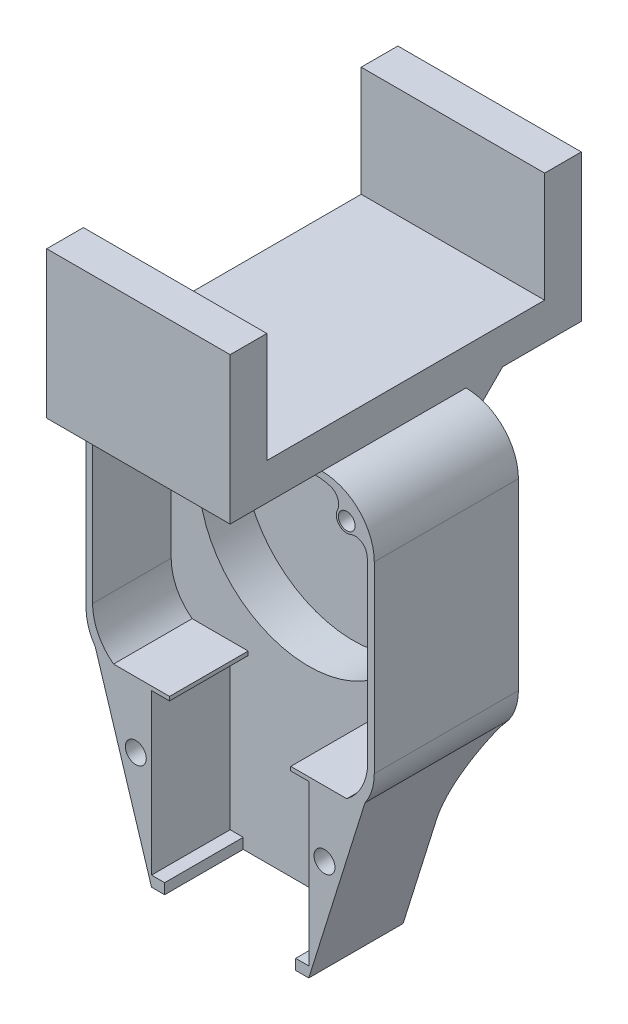
SolidWorks part; units mm, degrees
ref_plane "Alzado" through (0, 0, 0) normal (0, 0, 1) x (1, 0, 0)
ref_plane "Planta" through (0, 0, 0) normal (0, 1, 0) x (1, 0, 0)
ref_plane "Vista lateral" through (0, 0, 0) normal (1, 0, 0) x (0, 0, -1)
sketch "Croquis4" plane through (0, 0, 0) normal (0, 0, 1) x (1, 0, 0)
  line L9 (-17.5, 27.5) -> (17.5, 27.5)
  line L10 (-27.5, 17.5) -> (-27.5, -17.5)
  line L11 (-17.5, -27.5) -> (17.5, -27.5)
  line L12 (27.5, 17.5) -> (27.5, -17.5)
  line L13 (-27.5, 27.5) -> (27.5, -27.5) construction
  line L14 (-27.5, -27.5) -> (27.5, 27.5) construction
  circle A0 centre (0, 0) radius 2.5
  arc A1 (-27.5, -17.5) -> (-17.5, -27.5) centre (-17.5, -17.5) ccw
  arc A2 (17.5, -27.5) -> (27.5, -17.5) centre (17.5, -17.5) ccw
  arc A3 (17.5, 27.5) -> (27.5, 17.5) centre (17.5, 17.5) cw
  arc A4 (-17.5, 27.5) -> (-27.5, 17.5) centre (-17.5, 17.5) ccw
  point P0 (0, 0)
  dimension "D3" = 5
  dimension "D4" = 10
  dimension "D1" = 55
  dimension "D2" = 55
extrude "Saliente-Extruir1" add sketch "Croquis4" along normal blind 4
sketch "Croquis5" plane through (0, 0, 4) normal (0, 0, 1) x (1, 0, 0)
  line L1 (-17.5, 27.5) -> (17.5, 27.5)
  line L2 (-27.5, 17.5) -> (-27.5, -17.5)
  line L3 (-17.5, -27.5) -> (17.5, -27.5)
  line L4 (27.5, 17.5) -> (27.5, -17.5)
  line L5 (-27.5, 27.5) -> (27.5, -27.5) construction
  line L6 (-27.5, -27.5) -> (27.5, 27.5) construction
  circle A0 centre (0, 0) radius 21
  circle A1 centre (0, 0) radius 2.5 construction
  arc A2 (17.5, -27.5) -> (27.5, -17.5) centre (17.5, -17.5) ccw
  arc A3 (-27.5, -17.5) -> (-17.5, -27.5) centre (-17.5, -17.5) ccw
  arc A4 (17.5, 27.5) -> (27.5, 17.5) centre (17.5, 17.5) cw
  arc A5 (-17.5, 27.5) -> (-27.5, 17.5) centre (-17.5, 17.5) ccw
  point P4 (0, 0)
  dimension "D1" = 42
  dimension "D4" = 10
  dimension "D2" = 55
  dimension "D3" = 55
extrude "Saliente-Extruir2" add sketch "Croquis5" along normal blind 8.5
sketch "Croquis6" plane through (0, 0, 12.5) normal (0, 0, 1) x (1, 0, 0)
  line L1 (-25.7206, -23.194) -> (-15, -57.5)
  line L2 (-15, -57.5) -> (15, -57.5)
  line L3 (-17.5, -27.5) -> (17.5, -27.5) construction
  line L4 (15, -57.5) -> (25.7206, -23.194)
  line L8 (-17.5, -27.5) -> (17.5, -27.5)
  line L12 (25.119, -25.119) -> (27.5, -27.5) construction
  arc A1 (17.5, -27.5) -> (25.7206, -23.194) centre (17.5, -17.5) ccw
  arc A2 (-25.7206, -23.194) -> (-17.5, -27.5) centre (-17.5, -17.5) ccw
  point P5 (0, 0)
  dimension "D6" = 10
  dimension "D2" = 30
  dimension "D3" = 30
extrude "Saliente-Extruir4" add sketch "Croquis6" against normal blind 3
fillet "Redondeo1" radius 10 3 edges at (22.1401, -26.3583, 9.5) (-22.1401, -26.3583, 9.5) (0, -27.5, 9.5)
sketch "Croquis8" plane through (0, 0, 12.5) normal (0, 0, 1) x (1, 0, 0)
  line L0 (0, -57.5) -> (0, -20) construction
  line L1 (-15, -57.5) -> (15, -57.5) construction
  line L2 (-25.3906, -24.25) -> (-25.8417, -23.0151)
  line L3 (-15, -55.5) -> (-15, -25)
  line L4 (-17.5, 27.5) -> (17.5, 27.5)
  line L5 (12.5, -55.5) -> (15, -55.5)
  line L6 (-27.5, 17.5) -> (-27.5, -17.5)
  line L7 (-15, -25) -> (-11.5606, -25)
  line L8 (-11.5606, -25) -> (-11.5606, -24.25)
  line L9 (-11.5606, -24.25) -> (-25.3906, -24.25)
  line L10 (12.5, -57.5) -> (12.5, -55.5)
  line L11 (-25.7206, -23.194) -> (-15, -57.5) construction
  line L12 (-25.3906, -24.25) -> (-15, -57.5)
  line L13 (-15, -57.5) -> (-12.5, -57.5)
  line L14 (-12.5, -57.5) -> (-12.5, -55.5)
  line L15 (-12.5, -55.5) -> (-15, -55.5)
  line L16 (15, -57.5) -> (12.5, -57.5)
  line L17 (25.3906, -24.25) -> (15, -57.5)
  line L18 (11.5606, -24.25) -> (25.3906, -24.25)
  line L19 (11.5606, -25) -> (11.5606, -24.25)
  line L20 (15, -25) -> (11.5606, -25)
  line L21 (15, -55.5) -> (15, -25)
  line L23 (27.5, 17.5) -> (27.5, -17.5)
  line L24 (-27.5, 27.5) -> (27.5, -27.5) construction
  line L25 (-26.25, -26.25) -> (27.5, 27.5) construction
  line L26 (25.3906, -24.25) -> (25.862, -22.9843)
  line L28 (-16.25, 26.25) -> (16.25, 26.25)
  line L29 (-26.25, 16.25) -> (-26.25, -16.25)
  line L31 (26.25, 16.25) -> (26.25, -16.25)
  line L32 (-26.25, 26.25) -> (26.25, -26.25) construction
  line L33 (-26.25, -26.25) -> (26.25, 26.25) construction
  arc A9 (-27.5, -17.5) -> (-25.8417, -23.0151) centre (-17.5, -17.5) ccw
  arc A10 (25.862, -22.9843) -> (27.5, -17.5) centre (17.5, -17.5) ccw
  arc A11 (17.5, 27.5) -> (27.5, 17.5) centre (17.5, 17.5) cw
  arc A12 (-17.5, 27.5) -> (-27.5, 17.5) centre (-17.5, 17.5) ccw
  arc A13 (-26.25, -16.25) -> (-22.25, -24.25) centre (-16.25, -16.25) ccw
  arc A14 (22.25, -24.25) -> (26.25, -16.25) centre (16.25, -16.25) ccw
  arc A15 (16.25, 26.25) -> (19.0082, 25.8621) centre (16.25, 16.25) cw
  arc A16 (-16.25, 26.25) -> (-19.0082, 25.8621) centre (-16.25, 16.25) ccw
  arc A18 (-26.0816, 18.075) -> (-23.0104, 19.7822) centre (-23.865, 17.7034) cw
  arc A19 (-20.4641, 22.5324) -> (-19.0082, 25.8621) centre (-18.3575, 23.5944) cw
  arc A21 (-26.0727, 18.1248) -> (-26.25, 16.25) centre (-16.25, 16.25) ccw
  arc A22 (-23.0104, 19.7822) -> (-20.4641, 22.5324) centre (-22.25, 21.632) ccw
  arc A23 (26.0816, 18.075) -> (23.0104, 19.7822) centre (23.865, 17.7034) ccw
  arc A24 (20.4641, 22.5324) -> (19.0082, 25.8621) centre (18.3575, 23.5944) ccw
  arc A25 (23.0104, 19.7822) -> (20.4641, 22.5324) centre (22.25, 21.632) cw
  arc A26 (26.0727, 18.1248) -> (26.25, 16.25) centre (16.25, 16.25) cw
  circle A27 centre (-18, -36.75) radius 2
  circle A28 centre (18, -36.75) radius 2
  point P0 (0, 0)
  point P3 (0, 0)
  point P7 (0, -57.5)
  point P10 (0, 0)
  point P16 (0, -42.5)
  arc M7 (-27.5, -17.5) -> (-25.7206, -23.194) centre (-17.5, -17.5) ccw
  line M8 (-25.7206, -23.194) -> (-15, -57.5)
  line M9 (-15, -57.5) -> (15, -57.5)
  line M10 (15, -57.5) -> (25.7206, -23.194)
  arc M11 (25.7206, -23.194) -> (27.5, -17.5) centre (17.5, -17.5) ccw
  line M12 (27.5, -17.5) -> (27.5, 17.5)
  arc M13 (27.5, 17.5) -> (17.5, 27.5) centre (17.5, 17.5) ccw
  line M14 (17.5, 27.5) -> (-17.5, 27.5)
  arc M15 (-17.5, 27.5) -> (-27.5, 17.5) centre (-17.5, 17.5) ccw
  line M16 (-27.5, 17.5) -> (-27.5, -17.5)
  dimension "D3" = 55
  dimension "D4" = 55
  dimension "D7" = 52.5
  dimension "D9" = 10
  dimension "D10" = 12.5
  dimension "D5" = 10
  dimension "D6" = 52.5
  dimension "D8" = 15
  dimension "D11" = 90
  dimension "D12" = 3
  dimension "D13" = 4
  dimension "D14" = 32.5
  dimension "D20" = 0.75
  dimension "D21" = 90
  dimension "D22" = 90
  dimension "D23" = 2.5
  dimension "D24" = 2.5
  dimension "D25" = 2
extrude "Saliente-Extruir5" add sketch "Croquis8" along normal blind 15 contours A16 L28 A15 L31 A14 L18 L9 A13 L29 M10 M11 M12 M13 M14 M15 M16 M7 M8 | L14 L15 L3 L7 L8 L9 M8 M9 | L21 L5 L10 L18 L19 L20 M9 M10 region at (-24.8348, -23.4967, 12.5) region at (-23.8203, -24.6101, 12.5) region at (12.8601, -56.5, 12.5)
sketch "Croquis9" plane through (0, 0, 27.5) normal (0, 0, 1) x (1, 0, 0)
  line L0 (0, 23.4791) -> (0, 0) construction
  circle A0 centre (-22.25, 21.632) radius 1.6
  arc A1 (-23.0104, 19.7822) -> (-20.4641, 22.5324) centre (-22.25, 21.632) ccw construction
  circle A2 centre (-18, -36.75) radius 1.6
  circle A3 centre (-18, -36.75) radius 2 construction
  circle A4 centre (18, -36.75) radius 1.6
  circle A5 centre (22.25, 21.632) radius 1.6
  dimension "D1" = 3.2
  dimension "D2" = 3.2
extrude "Cortar-Extruir1" cut sketch "Croquis9" against normal through all
sketch "Croquis11" plane through (0, 27.5, 0) normal (0, 1, 0) x (1, 0, 0)
  line L0 (17.5, 0) -> (-17.5, 0) construction
  line L1 (-17.5, 15) -> (17.5, 15)
  line L2 (-17.5, 15) -> (-17.5, -38)
  line L3 (-17.5, -38) -> (17.5, -38)
  line L4 (17.5, 15) -> (17.5, -38)
  point P4 (0, 15)
  dimension "D1" = 53
  dimension "D2" = 35
  dimension "D3" = 15
extrude "Saliente-Extruir7" add sketch "Croquis11" along normal blind 7
sketch "Croquis12" plane through (0, 27.5, 0) normal (0, -1, 0) x (1, 0, 0)
  line L0 (-17.5, 38) -> (17.5, 38) construction
  line L1 (-17.5, 38) -> (17.5, 38)
  line L2 (-17.5, 38) -> (-17.5, 45)
  line L3 (-17.5, 45) -> (17.5, 45)
  line L4 (17.5, 38) -> (17.5, 45)
  line L5 (-17.5, -15) -> (17.5, -15)
  line L6 (-17.5, -15) -> (-17.5, -22)
  line L7 (-17.5, -22) -> (17.5, -22)
  line L8 (17.5, -15) -> (17.5, -22)
  line L9 (17.5, -15) -> (-17.5, -15) construction
  dimension "D1" = 7
  dimension "D2" = 7
  dimension "D3" = 35
  dimension "D4" = 35
extrude "Saliente-Extruir8" add sketch "Croquis12" against normal blind 28
chamfer "Chaflán2" distance 7 angle 45 1 edges at (0, 27.5, 0)
sketch "Croquis13" plane through (0, 0, 0) normal (0, 0, -1) x (-1, 0, 0)
  circle A0 centre (0, 0) radius 11.4
  dimension "D1" = 22.8
extrude "Cortar-Extruir2" cut sketch "Croquis13" against normal blind 2
